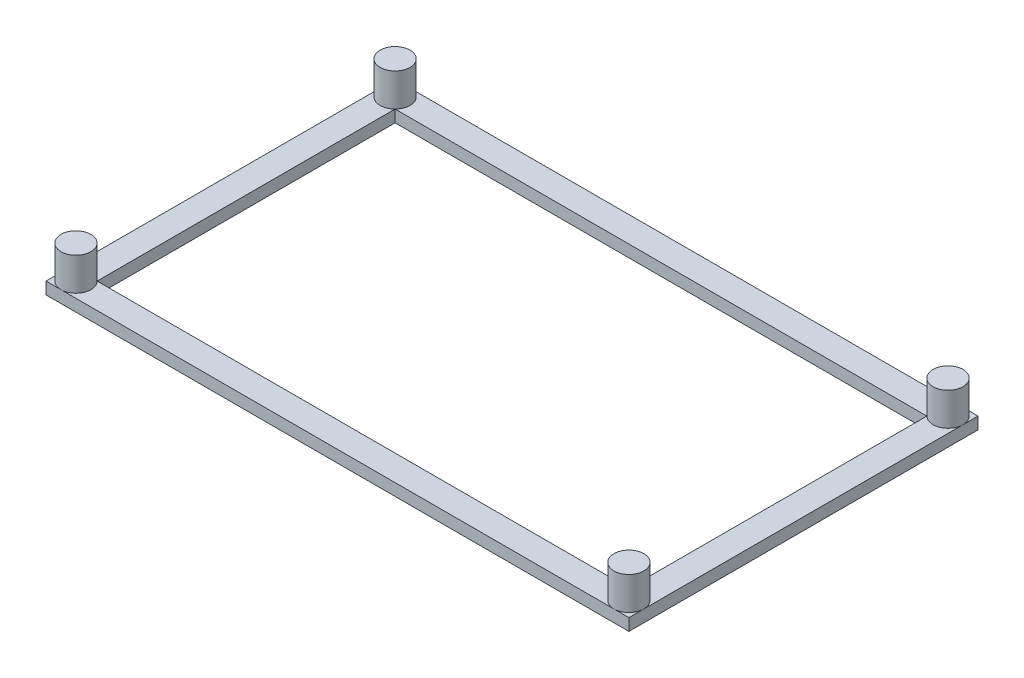
SolidWorks part; units mm, degrees
ref_plane "Front Plane" through (0, 0, 0) normal (0, 0, 1) x (1, 0, 0)
ref_plane "Top Plane" through (0, 0, 0) normal (0, 1, 0) x (1, 0, 0)
ref_plane "Right Plane" through (0, 0, 0) normal (1, 0, 0) x (0, 0, -1)
sketch "Sketch4" plane through (0, 0, 0) normal (0, 1, 0) x (1, 0, 0)
  circle A0 centre (0.3415, 62.6915) radius 1.8415 construction
  circle A1 centre (92.6585, 62.6915) radius 1.8415 construction
  circle A2 centre (92.6585, 115.9685) radius 1.8415 construction
  circle A3 centre (0.3415, 115.9685) radius 1.8415 construction
  circle A4 centre (0.3415, 62.6915) radius 1.8415
  circle A5 centre (92.6585, 62.6915) radius 1.8415
  circle A6 centre (92.6585, 115.9685) radius 1.8415
  circle A7 centre (0.3415, 115.9685) radius 1.8415
  circle A8 centre (0.3415, 115.9685) radius 2.5
  circle A9 centre (0.3415, 62.6915) radius 2.5
  circle A10 centre (92.6585, 62.6915) radius 2.5
  circle A11 centre (92.6585, 115.9685) radius 2.5
  dimension "D1" = 5
extrude "Boss-Extrude4" add sketch "Sketch4" along normal blind 7.5 separate body contours A10 A5 | A5 | A9 A4 | A4 | A8 A7 | A7 | A6 | A11 A6 region at (0.3415, 0, -62.6915) region at (92.6585, 0, -62.6915) region at (92.6585, 0, -115.9685) region at (0.3415, 0, -115.9685) region at (-2.0878, 0, -115.9685) region at (-2.0878, 0, -62.6915) region at (90.2292, 0, -62.6915) region at (90.2292, 0, -115.9685)
sketch "Sketch5" plane through (0, 0, 0) normal (0, -1, 0) x (1, 0, 0)
  line L0 (-2.1585, -118.4685) -> (2.1093, -114.2007) construction
  line L1 (-2.1585, -60.1915) -> (95.1585, -60.1915)
  line L2 (-2.1585, -60.1915) -> (-2.1585, -118.4685)
  line L3 (-2.1585, -118.4685) -> (95.1585, -118.4685)
  line L4 (95.1585, -60.1915) -> (95.1585, -118.4685)
  line L5 (2.1093, -64.4593) -> (90.8907, -64.4593)
  line L6 (2.1093, -64.4593) -> (2.1093, -114.2007)
  line L7 (2.1093, -114.2007) -> (90.8907, -114.2007)
  line L8 (90.8907, -64.4593) -> (90.8907, -114.2007)
  line L9 (0.3415, -115.9685) -> (2.1093, -114.2007) construction
  circle A0 centre (92.6585, -115.9685) radius 2.5 construction
  circle A1 centre (0.3415, -62.6915) radius 2.5 construction
  circle A2 centre (0.3415, -115.9685) radius 2.5 construction
  circle A3 centre (92.6585, -62.6915) radius 2.5 construction
extrude "Boss-Extrude5" add sketch "Sketch5" against normal blind 2
